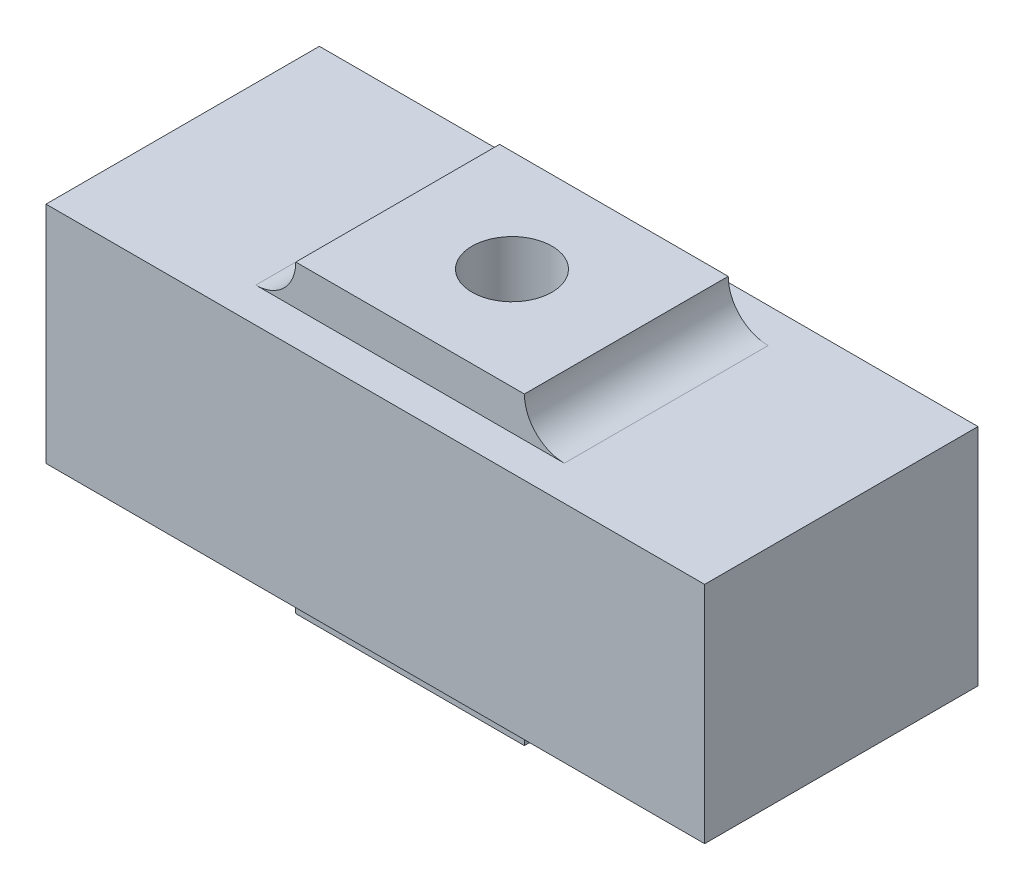
SolidWorks part; units mm, degrees
ref_plane "Front Plane" through (0, 0, 0) normal (0, 0, 1) x (1, 0, 0)
ref_plane "Top Plane" through (0, 0, 0) normal (0, 1, 0) x (1, 0, 0)
ref_plane "Right Plane" through (0, 0, 0) normal (1, 0, 0) x (0, 0, -1)
sketch "Sketch1" plane through (0, 0, 0) normal (0, 1, 0) x (1, 0, 0)
  line L1 (-20.6, -8.55) -> (20.6, -8.55)
  line L2 (-20.6, -8.55) -> (-20.6, 8.55)
  line L3 (-20.6, 8.55) -> (20.6, 8.55)
  line L4 (20.6, -8.55) -> (20.6, 8.55)
  line L5 (-20.6, -8.55) -> (20.6, 8.55) construction
  line L6 (-20.6, 8.55) -> (20.6, -8.55) construction
  point P0 (0, 0)
  dimension "D1" = 17.1
  dimension "D2" = 41.2
extrude "Boss-Extrude1" add sketch "Sketch1" along normal blind 14.05
sketch "Sketch2" plane through (0, 14.05, 0) normal (0, 1, 0) x (1, 0, 0)
  line L1 (-7.15, -6.375) -> (7.15, -6.375)
  line L2 (-7.15, -6.375) -> (-7.15, 6.375)
  line L3 (-7.15, 6.375) -> (7.15, 6.375)
  line L4 (7.15, -6.375) -> (7.15, 6.375)
  line L5 (-7.15, -6.375) -> (7.15, 6.375) construction
  line L6 (-7.15, 6.375) -> (7.15, -6.375) construction
  point P0 (0, 0)
  dimension "D1" = 12.75
  dimension "D2" = 14.3
extrude "Boss-Extrude2" add sketch "Sketch2" against normal offset from surface (19.05 mm away) 2.5 from offset 2.5 up to face at (0, 0, 0) offset beyond the face yes
fillet "Fillet1" radius 2.5 4 edges at (7.15, 0, 0) (-7.15, 0, 0) (-7.15, 14.05, 0) (7.15, 14.05, 0)
sketch "Sketch3" plane through (0, 16.55, 0) normal (0, 1, 0) x (1, 0, 0)
  circle A0 centre (0, 0) radius 2.5
  dimension "D1" = 5
extrude "Cut-Extrude1" cut sketch "Sketch3" against normal through all
